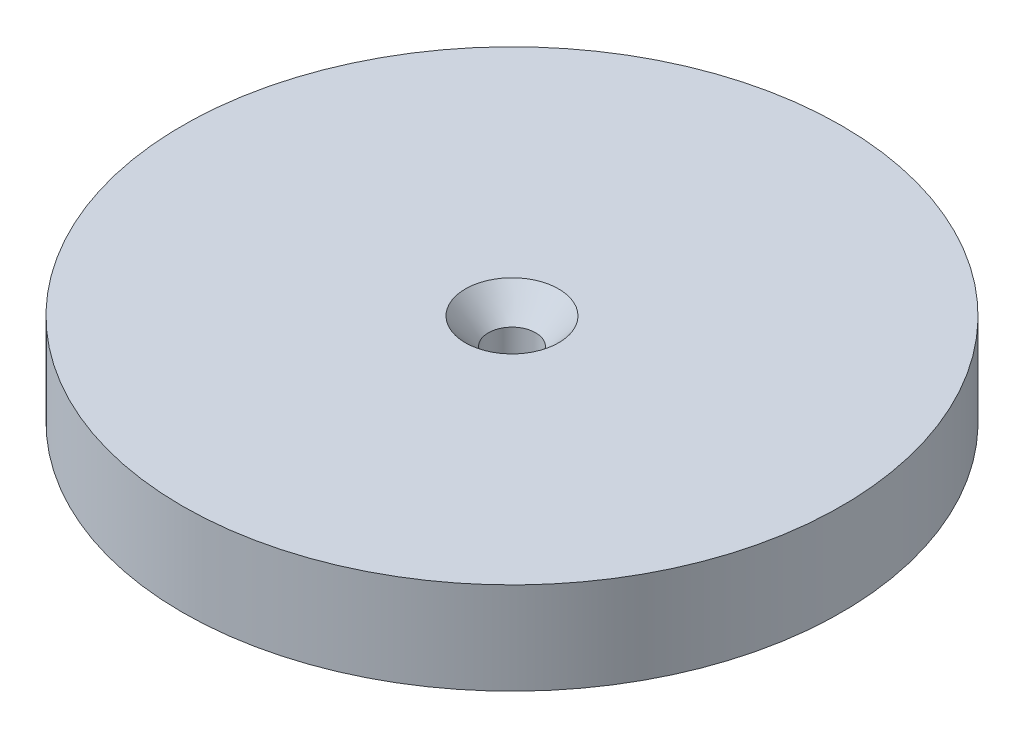
SolidWorks part; units mm, degrees
ref_plane "Front Plane" through (0, 0, 0) normal (0, 0, 1) x (1, 0, 0)
ref_plane "Top Plane" through (0, 0, 0) normal (0, 1, 0) x (1, 0, 0)
ref_plane "Right Plane" through (0, 0, 0) normal (1, 0, 0) x (0, 0, -1)
sketch "Sketch1" plane through (0, 0, 0) normal (0, 1, 0) x (1, 0, 0)
  circle A0 centre (0, 0) radius 20.066 construction
  circle A1 centre (0, 0) radius 45.466
  dimension "D1" = 25.4
extrude "Boss-Extrude1" add sketch "Sketch1" along normal blind 25.4
sketch "Sketch3" plane through (0, 0, 0) normal (0, -1, 0) x (1, 0, 0)
  circle A0 centre (0, 0) radius 20.32
extrude "Cut-Extrude1" cut sketch "Sketch3" against normal blind 12.7
hole_wizard "CSK for 1/4 Flat Head Machine Screw1" positions "Sketch6" profile "Sketch7" countersink size "1/4" standard "ANSI Inch"
sketch "Sketch6" plane through (0, 25.4, 0) normal (0, 1, 0) x (1, 0, 0)
  point P0 (0, 0)
sketch "Sketch7" plane through (0, 25.4, 0) normal (1, 0, 0) x (0, 0, 1)
  line L0 (0, 0) -> (0, 27.3611)
  line L1 (0, 27.3611) -> (3.2639, 25.4)
  line L2 (3.2639, 25.4) -> (3.2639, 3.6524)
  line L3 (3.2639, 3.6524) -> (6.4389, 0)
  line L5 (6.4389, 0) -> (0, 0)
  line L6 (-3.2639, 3.6524) -> (-6.4389, 0) construction
  line L10 (0, 27.3611) -> (-3.2639, 25.4) construction
  line L11 (0, -6.35) -> (0, 107.95) construction
  dimension "Hole Dia." = 6.5278
  dimension "Hole Depth" = 25.4
  dimension "Near C'Sink Dia." = 12.8778
  dimension "Near C'Sink Angle" = 82
  dimension "Drill Angle" = 118
sketch "Sketch9" plane through (0, 0, 0) normal (0, -1, 0) x (1, 0, 0)
  circle A0 centre (0, 0) radius 53.0319
extrude "Cut-Extrude3" cut sketch "Sketch9" against normal blind 12.7
